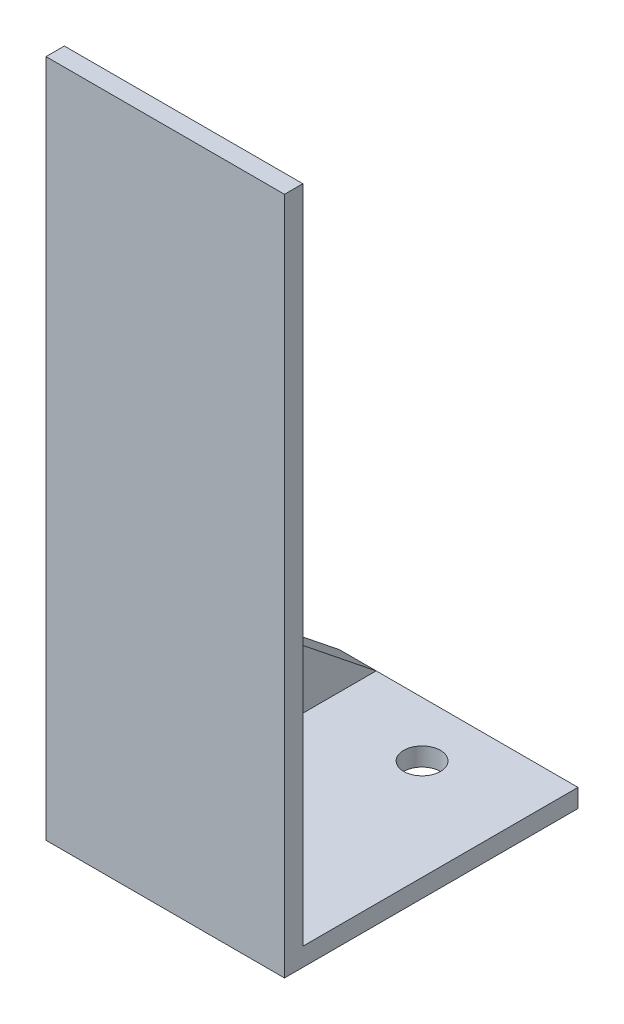
SolidWorks part; units mm, degrees
ref_plane "Front Plane" through (0, 0, 0) normal (0, 0, 1) x (1, 0, 0)
ref_plane "Top Plane" through (0, 0, 0) normal (0, 1, 0) x (1, 0, 0)
ref_plane "Right Plane" through (0, 0, 0) normal (1, 0, 0) x (0, 0, -1)
sketch "Sketch1" plane through (0, 0, 0) normal (1, 0, 0) x (0, 0, -1)
  line L5 (0, 0) -> (-101.6, 0)
  line L6 (0, 0) -> (0, 6.35)
  line L11 (0, 6.35) -> (-95.25, 6.35)
  line L12 (-101.6, 0) -> (-101.6, 6.35)
  line L14 (-101.6, 6.35) -> (-101.6, 234.95)
  line L15 (-101.6, 234.95) -> (-95.25, 234.95)
  line L16 (-95.25, 6.35) -> (-95.25, 234.95)
  point P0 (0, 0)
  dimension "D1" = 101.6
  dimension "D2" = 6.35
  dimension "D3" = 234.95
  dimension "D4" = 6.35
  dimension "D5" = 6.35
extrude "Boss-Extrude1" add sketch "Sketch1" along normal blind 146.05
sketch "Sketch2" plane through (0, 0, 101.6) normal (0, 0, 1) x (1, 0, 0)
  line L1 (0, 0) -> (63.5, 0)
  line L2 (0, 0) -> (0, 234.95)
  line L3 (0, 234.95) -> (63.5, 234.95)
  line L4 (63.5, 0) -> (63.5, 234.95)
  dimension "D1" = 234.95
  dimension "D2" = 63.5
extrude "Cut-Extrude1" cut sketch "Sketch2" against normal blind 146.05
sketch "Sketch3" plane through (63.5, 0, 0) normal (-1, 0, 0) x (0, 0, 1)
  line L5 (0, 6.35) -> (95.25, 82.55)
  line L6 (95.25, 6.35) -> (95.25, 234.95) construction
  line L7 (95.25, 82.55) -> (95.25, 6.35)
  line L8 (95.25, 6.35) -> (0, 6.35)
  dimension "D1" = 76.2
extrude "Boss-Extrude2" add sketch "Sketch3" against normal blind 12.7
sketch "Sketch4" plane through (0, 6.35, 0) normal (0, 1, 0) x (1, 0, 0)
  circle A0 centre (111.125, -19.05) radius 6.35
  circle A1 centre (111.125, -82.55) radius 6.35
  point P4 (0, 0)
  point P5 (0, 0)
  point P7 (0, 0)
  dimension "D1" = 12.7
  dimension "D2" = 12.7
  dimension "D3" = 34.925
  dimension "D4" = 19.05
  dimension "D5" = 19.05
extrude "Cut-Extrude2" cut sketch "Sketch4" against normal blind 12.7
